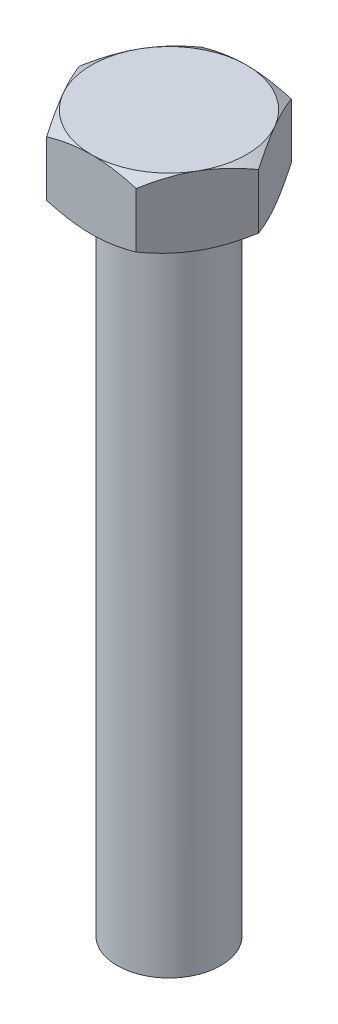
SolidWorks part; units mm, degrees
ref_plane "Front Plane" through (0, 0, 0) normal (0, 0, 1) x (1, 0, 0)
ref_plane "Top Plane" through (0, 0, 0) normal (0, 1, 0) x (1, 0, 0)
ref_plane "Right Plane" through (0, 0, 0) normal (1, 0, 0) x (0, 0, -1)
ref_axis "Axis_X" through (-88.99, 0, 0) along (1, 0, 0)
ref_axis "Axis_Y" through (0, 55, 0) along (0, -1, 0)
ref_axis "Axis_Z" through (0, 0, -88.99) along (0, 0, 1)
sketch "Sketch1" plane through (0, 0, 0) normal (0, 1, 0) x (1, 0, 0)
  line L1 (5.1962, 9) -> (-5.1962, 9)
  line L2 (-5.1962, 9) -> (-10.3923, 0)
  line L3 (-10.3923, 0) -> (-5.1962, -9)
  line L4 (-5.1962, -9) -> (5.1962, -9)
  line L5 (5.1962, -9) -> (10.3923, 0)
  line L6 (10.3923, 0) -> (5.1962, 9)
  circle A0 centre (0, 0) radius 9 construction
  dimension "FIX_1" = 18
extrude "Boss-Extrude1" add sketch "Sketch1" along normal blind 8
sketch "Sketch2" plane through (0, 0, 0) normal (0, 0, 1) x (1, 0, 0)
  line L0 (-10.3923, 0) -> (-9, 0)
  line L1 (-9, 0) -> (-10.3923, 0.8038)
  line L2 (-10.3923, 8) -> (-10.3923, 0) construction
  line L3 (-10.3923, 0.8038) -> (-10.3923, 0)
  line L6 (-10.3923, 8) -> (-9, 8)
  line L7 (-10.3923, 8) -> (-5.1962, 8) construction
  line L8 (-9, 8) -> (-10.3923, 7.1962)
  line L9 (-10.3923, 7.1962) -> (-10.3923, 8)
  dimension "FIX_3" = 30
revolve "Cut-Revolve1" cut sketch "Sketch2" angle 360 about axis through (0, 55, 0) along (0, -1, 0)
sketch "Sketch3" plane through (0, 0, 0) normal (0, -1, 0) x (1, 0, 0)
  circle A0 centre (0, 0) radius 6
  dimension "FIX_5" = 12
extrude "Boss-Extrude2" add sketch "Sketch3" along normal blind 75
cosmetic thread "Thread1" parameters "FIX_7"=10.106
equation "\"Factor\"= 1.082532"
